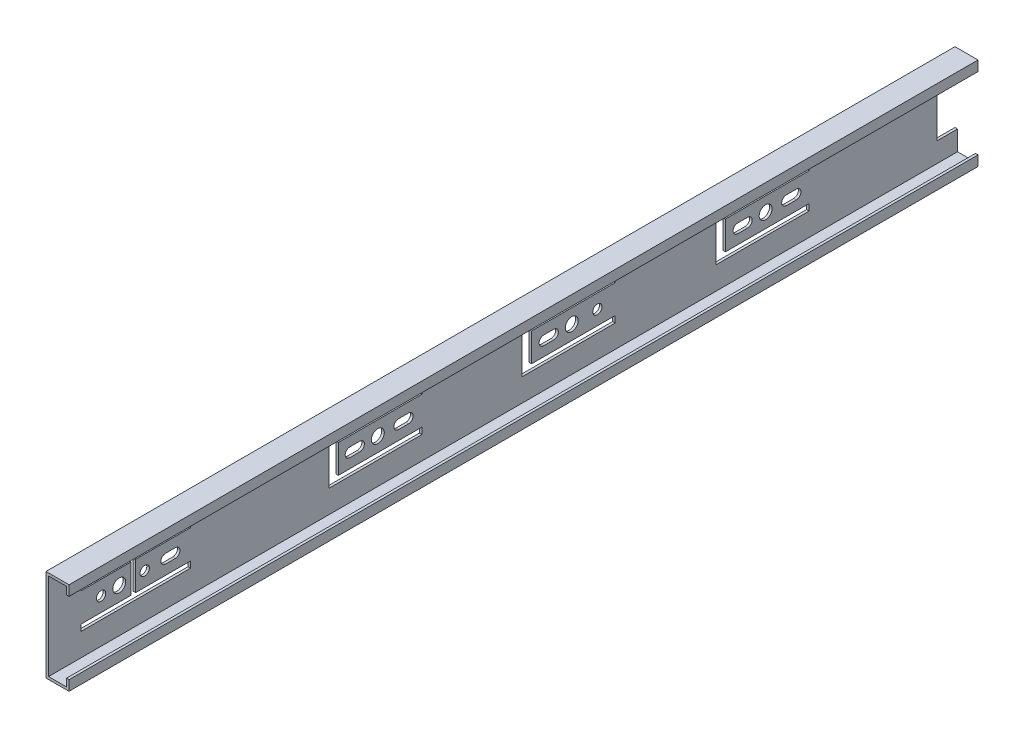
SolidWorks part; units mm, degrees
ref_plane "Front Plane" through (0, 0, 0) normal (0, 0, 1) x (1, 0, 0)
ref_plane "Top Plane" through (0, 0, 0) normal (0, 1, 0) x (1, 0, 0)
ref_plane "Right Plane" through (0, 0, 0) normal (1, 0, 0) x (0, 0, -1)
ref_plane "Plane1" through (5.7, 0, 0) normal (1, 0, 0) x (0, 0, -1)
sketch "Sketch1" plane through (5.7, 0, 0) normal (1, 0, 0) x (0, 0, -1)
  line L0 (0, -22.85) -> (0, 22.85)
  line L1 (0, 22.85) -> (-450, 22.85)
  line L2 (-450, 22.85) -> (-450, -22.85)
  line L3 (-450, -22.85) -> (0, -22.85)
extrude "Boss-Extrude1" add sketch "Sketch1" against normal blind 11.4
sketch "Sketch2" plane through (0, 0, 450) normal (0, 0, 1) x (1, 0, 0)
  line L0 (5.7, 17.85) -> (4.43, 17.85)
  line L1 (4.43, 17.85) -> (4.43, 21.58)
  line L2 (4.43, 21.58) -> (-4.43, 21.58)
  line L3 (-4.43, 21.58) -> (-4.43, -21.58)
  line L4 (-4.43, -21.58) -> (4.43, -21.58)
  line L5 (4.43, -21.58) -> (4.43, -17.85)
  line L6 (4.43, -17.85) -> (5.7, -17.85)
  line L7 (5.7, -17.85) -> (5.7, 17.85)
extrude "Cut-Extrude1" cut sketch "Sketch2" against normal through all
sketch "Sketch3" plane through (-5.7, 0, 0) normal (-1, 0, 0) x (0, 0, 1)
  line L0 (0, 11.8) -> (0, -11.8)
  line L1 (0, -11.8) -> (10.25, -11.8)
  line L2 (10.25, -11.8) -> (10.25, 11.8)
  line L3 (10.25, 11.8) -> (0, 11.8)
extrude "Cut-Extrude2" cut sketch "Sketch3" against normal through all
sketch "Sketch4" plane through (-4.43, 0, 0) normal (1, 0, 0) x (0, 0, -1)
  line L0 (-169.5, -10.25) -> (-169.5, -7.05)
  line L1 (-169.5, -7.05) -> (-210.9, -7.05)
  line L2 (-210.9, -7.05) -> (-210.9, 7.05)
  line L3 (-210.9, 7.05) -> (-169.5, 7.05)
  line L4 (-169.5, 7.05) -> (-169.5, 10.25)
  line L5 (-169.5, 10.25) -> (-215.5, 10.25)
  line L6 (-215.5, 10.25) -> (-215.5, -10.25)
  line L7 (-215.5, -10.25) -> (-169.5, -10.25)
extrude "Cut-Extrude3" cut sketch "Sketch4" against normal through all
sketch "Sketch5" plane through (-4.43, 0, 0) normal (1, 0, 0) x (0, 0, -1)
  line L0 (-119.5, -10.25) -> (-73.5, -10.25)
  line L1 (-73.5, -10.25) -> (-73.5, -7.05)
  line L2 (-73.5, -7.05) -> (-114.9, -7.05)
  line L3 (-114.9, -7.05) -> (-114.9, 7.05)
  line L4 (-114.9, 7.05) -> (-73.5, 7.05)
  line L5 (-73.5, 7.05) -> (-73.5, 10.25)
  line L6 (-73.5, 10.25) -> (-119.5, 10.25)
  line L7 (-119.5, 10.25) -> (-119.5, -10.25)
extrude "Cut-Extrude4" cut sketch "Sketch5" against normal through all
sketch "Sketch6" plane through (-4.43, 0, 0) normal (1, 0, 0) x (0, 0, -1)
  line L0 (-265.15, 7.05) -> (-265.15, 10.25)
  line L1 (-265.15, 10.25) -> (-311.15, 10.25)
  line L2 (-311.15, 10.25) -> (-311.15, -10.25)
  line L3 (-311.15, -10.25) -> (-265.15, -10.25)
  line L4 (-265.15, -10.25) -> (-265.15, -7.05)
  line L5 (-265.15, -7.05) -> (-306.55, -7.05)
  line L6 (-306.55, -7.05) -> (-306.55, 7.05)
  line L7 (-306.55, 7.05) -> (-265.15, 7.05)
extrude "Cut-Extrude5" cut sketch "Sketch6" against normal through all
sketch "Sketch7" plane through (-4.43, 0, 0) normal (1, 0, 0) x (0, 0, -1)
  line L0 (-79.85, 2.3) -> (-84.75, 2.3)
  line L1 (-84.75, -2.3) -> (-79.85, -2.3)
  arc A0 (-79.85, -2.3) -> (-79.85, 2.3) centre (-79.85, 0) ccw
  arc A1 (-84.75, 2.3) -> (-84.75, -2.3) centre (-84.75, 0) ccw
extrude "Cut-Extrude6" cut sketch "Sketch7" against normal through all
sketch "Sketch8" plane through (-4.43, 0, 0) normal (1, 0, 0) x (0, 0, -1)
  line L0 (-108.85, -2.3) -> (-103.95, -2.3)
  line L1 (-103.95, 2.3) -> (-108.85, 2.3)
  arc A0 (-103.95, -2.3) -> (-103.95, 2.3) centre (-103.95, 0) ccw
  arc A1 (-108.85, 2.3) -> (-108.85, -2.3) centre (-108.85, 0) ccw
extrude "Cut-Extrude7" cut sketch "Sketch8" against normal through all
sketch "Sketch9" plane through (-4.43, 0, 0) normal (1, 0, 0) x (0, 0, -1)
  line L0 (-387.25, 2.3) -> (-392.15, 2.3)
  line L1 (-392.15, -2.3) -> (-387.25, -2.3)
  arc A0 (-387.25, -2.3) -> (-387.25, 2.3) centre (-387.25, 0) ccw
  arc A1 (-392.15, 2.3) -> (-392.15, -2.3) centre (-392.15, 0) ccw
extrude "Cut-Extrude8" cut sketch "Sketch9" against normal through all
sketch "Sketch10" plane through (-4.43, 0, 0) normal (1, 0, 0) x (0, 0, -1)
  line L0 (-199.95, 2.3) -> (-204.85, 2.3)
  line L1 (-204.85, -2.3) -> (-199.95, -2.3)
  arc A0 (-204.85, 2.3) -> (-204.85, -2.3) centre (-204.85, 0) ccw
  arc A1 (-199.95, -2.3) -> (-199.95, 2.3) centre (-199.95, 0) ccw
extrude "Cut-Extrude9" cut sketch "Sketch10" against normal through all
sketch "Sketch11" plane through (-4.43, 0, 0) normal (1, 0, 0) x (0, 0, -1)
  line L0 (-295.95, 2.3) -> (-300.85, 2.3)
  line L1 (-300.85, -2.3) -> (-295.95, -2.3)
  arc A0 (-295.95, -2.3) -> (-295.95, 2.3) centre (-295.95, 0) ccw
  arc A1 (-300.85, 2.3) -> (-300.85, -2.3) centre (-300.85, 0) ccw
extrude "Cut-Extrude10" cut sketch "Sketch11" against normal through all
sketch "Sketch12" plane through (-4.43, 0, 0) normal (1, 0, 0) x (0, 0, -1)
  line L0 (-271.85, 2.3) -> (-276.75, 2.3)
  line L1 (-276.75, -2.3) -> (-271.85, -2.3)
  arc A0 (-276.75, 2.3) -> (-276.75, -2.3) centre (-276.75, 0) ccw
  arc A1 (-271.85, -2.3) -> (-271.85, 2.3) centre (-271.85, 0) ccw
extrude "Cut-Extrude11" cut sketch "Sketch12" against normal through all
sketch "Sketch13" plane through (-5.7, 0, 0) normal (-1, 0, 0) x (0, 0, 1)
  line L0 (434, -7.15) -> (409.2, -7.15)
  line L1 (409.2, -7.15) -> (409.2, 7.15)
  line L2 (409.2, 7.15) -> (434, 7.15)
  line L3 (434, 7.15) -> (434, 10.25)
  line L4 (434, 10.25) -> (379.65, 10.25)
  line L5 (379.65, 10.25) -> (379.65, 7.15)
  line L6 (379.65, 7.15) -> (406.9, 7.15)
  line L7 (406.9, 7.15) -> (406.9, -7.15)
  line L8 (406.9, -7.15) -> (379.65, -7.15)
  line L9 (379.65, -7.15) -> (379.65, -10.25)
  line L10 (379.65, -10.25) -> (434, -10.25)
  line L11 (434, -10.25) -> (434, -7.15)
extrude "Cut-Extrude12" cut sketch "Sketch13" against normal through all
hole_wizard "Ø6.4 (6.4) Diameter Hole1" positions "Sketch15" profile "Sketch14" hole size "Ø6.4" standard "ANSI Metric"
sketch "Sketch15" plane through (-5.7, 0, 0) normal (-1, 0, 0) x (0, 0, 1)
  point P0 (415, 0)
  point P1 (287, 0)
  point P2 (191, 0)
  point P3 (95, 0)
sketch "Sketch14" plane through (-5.7, 0, 415) normal (0, 1, 0) x (0, 0, 1)
  line L0 (0, 0) -> (0, 11.4)
  line L1 (0, 11.4) -> (3.2, 11.4)
  line L2 (3.2, 11.4) -> (3.2, 0)
  line L5 (3.2, 0) -> (0, 0)
  line L11 (0, -6.35) -> (0, 107.95) construction
  dimension "Thru Hole Dia." = 6.4
  dimension "Thru Hole Depth" = 11.4
hole_wizard "Ø4.6 (4.6) Diameter Hole1" positions "Sketch17" profile "Sketch16" hole size "Ø4.6" standard "ANSI Metric"
sketch "Sketch17" plane through (-5.7, 0, 0) normal (-1, 0, 0) x (0, 0, 1)
  point P0 (424, 0)
  point P1 (402.4, 0)
  point P2 (178.3, 0)
sketch "Sketch16" plane through (-5.7, 0, 424) normal (0, 1, 0) x (0, 0, 1)
  line L0 (0, 0) -> (0, 11.4)
  line L1 (0, 11.4) -> (2.3, 11.4)
  line L2 (2.3, 11.4) -> (2.3, 0)
  line L5 (2.3, 0) -> (0, 0)
  line L11 (0, -6.35) -> (0, 107.95) construction
  dimension "Thru Hole Dia." = 4.6
  dimension "Thru Hole Depth" = 11.4
